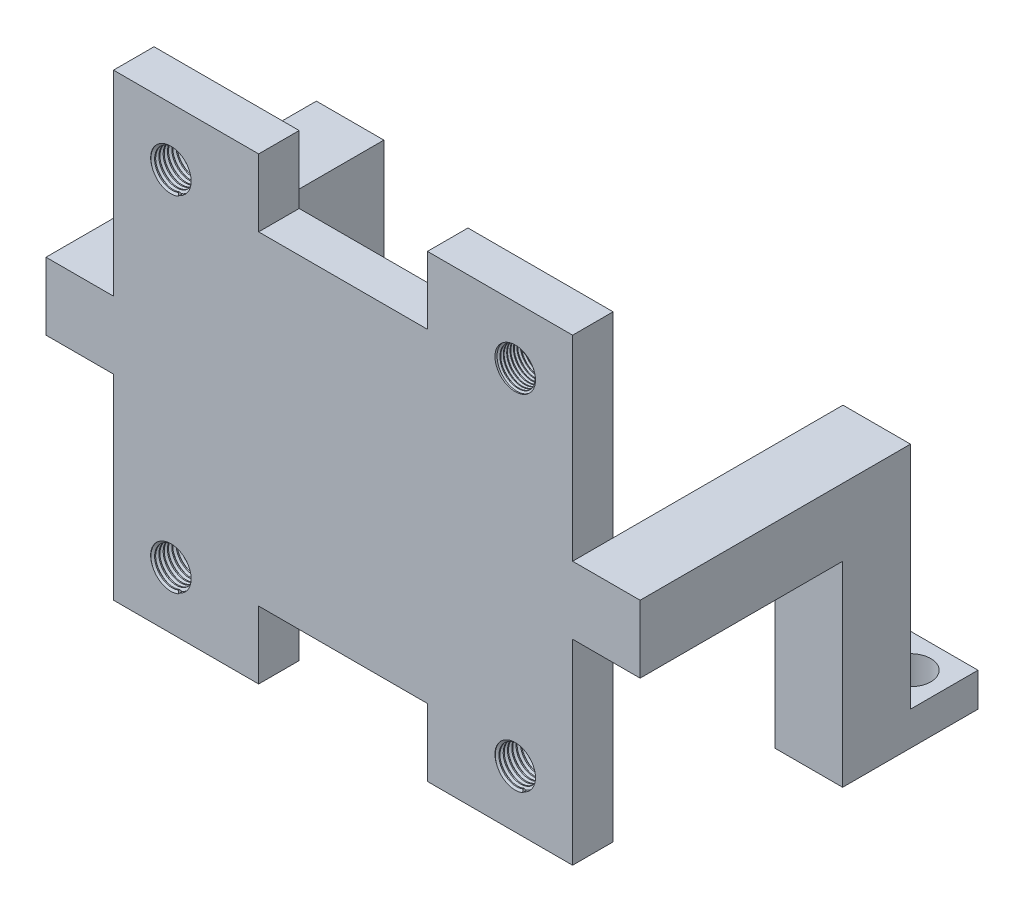
SolidWorks part; units mm, degrees
ref_plane "Front Plane" through (0, 0, 0) normal (0, 0, 1) x (1, 0, 0)
ref_plane "Top Plane" through (0, 0, 0) normal (0, 1, 0) x (1, 0, 0)
ref_plane "Right Plane" through (0, 0, 0) normal (1, 0, 0) x (0, 0, -1)
sketch "Sketch1" plane through (0, 0, 0) normal (0, 0, 1) x (1, 0, 0)
  line L0 (0, 0) -> (0, -34)
  line L1 (0, -34) -> (34, -34)
  line L2 (34, -34) -> (34, 0)
  line L3 (34, 0) -> (0, 0)
  dimension "D1" = 34
  dimension "D2" = 34
extrude "Boss-Extrude1" add sketch "Sketch1" along normal blind 3
sketch "Sketch2" plane through (0, 0, 0) normal (0, 0, -1) x (-1, 0, 0)
  line L0 (-17, 0) -> (-17, -34) construction
  line L1 (-34, 0) -> (0, 0) construction
  line L2 (0, -34) -> (-34, -34) construction
  line L3 (-34, -17) -> (0, -17) construction
  line L4 (-34, -34) -> (-34, 0) construction
  line L5 (0, 0) -> (0, -34) construction
  line L6 (-23.25, -5) -> (-10.75, -5)
  line L7 (-10.75, -5) -> (-10.75, 0)
  line L8 (-10.75, 0) -> (-23.25, 0)
  line L9 (-23.25, -5) -> (-23.25, 0)
  line L10 (-10.75, -29) -> (-10.75, -34)
  line L11 (-23.25, -29) -> (-10.75, -29)
  line L12 (-23.25, -29) -> (-23.25, -34)
  line L13 (-10.75, -34) -> (-23.25, -34)
  point P17 (-17, -5)
  dimension "D1" = 6.25
  dimension "D2" = 5
extrude "Cut-Extrude1" cut sketch "Sketch2" against normal through all contours L8 L9 L6 L7 | L10 L13 L12 L11
sketch "Sketch3" plane through (0, 0, 0) normal (0, 0, -1) x (-1, 0, 0)
  line L0 (-34, -34) -> (-34, 0) construction
  line L1 (-34, 0) -> (-23.25, 0) construction
  line L2 (-17, -5) -> (-17, -29) construction
  line L3 (-23.25, -5) -> (-10.75, -5) construction
  line L4 (-23.25, -29) -> (-10.75, -29) construction
  line L5 (-34, -17) -> (0, -17) construction
  line L6 (0, 0) -> (0, -34) construction
  circle A0 centre (-29.75, -4.25) radius 1.5
  circle A2 centre (-4.25, -4.25) radius 1.5
  circle A3 centre (-4.25, -29.75) radius 1.5
  circle A4 centre (-29.75, -29.75) radius 1.5
  dimension "D1" = 4.25
  dimension "D2" = 4.25
  dimension "D3" = 25.5
extrude "Cut-Extrude2" cut sketch "Sketch3" against normal through all contours A0 | A4 | A3 | A2
thread "Thread1" pitch 0.25 method extrude profile "Thread Profile1" start angle 0, offset 0, length 2.8, pitch 0.25, diameter 3
ref_plane "Plane1" through (31.25, -4.25, 0) normal (0, -1, 0) x (1, 0, 0)
sketch "Thread Profile1" plane through (31.25, -4.25, 0) normal (0, -1, 0) x (1, 0, 0)
  line L0 (0, 0) -> (0, 0.25) construction
  line L11 (0, 0) -> (0, 0.2187)
  line L12 (0, 0.2187) -> (-0.1353, 0.1406)
  line L13 (-0.1353, 0.1406) -> (-0.1353, 0.0781)
  line L15 (-0.1353, 0.0781) -> (0, 0)
  line L17 (-0.1353, 0.1094) -> (0, 0.1094) construction
  point P2 (0, 0)
  dimension "Pitch" = 0.25
  dimension "Profile_Angle" = 60
  dimension "Profile_Land" = 0.0625
  dimension "Profile_Height" = 0.1353
thread "Thread2" pitch 0.3175 method extrude profile "Thread Profile2" start angle 0, offset 0, length 2.8, pitch 0.3175, diameter 3
ref_plane "Plane2" through (5.75, -4.25, 0) normal (0, -1, 0) x (1, 0, 0)
sketch "Thread Profile2" plane through (5.75, -4.25, 0) normal (0, -1, 0) x (1, 0, 0)
  line L0 (0, 0) -> (0, 0.3175) construction
  line L11 (0, 0) -> (0, 0.2778)
  line L12 (0, 0.2778) -> (-0.1719, 0.1786)
  line L13 (-0.1719, 0.1786) -> (-0.1719, 0.0992)
  line L15 (-0.1719, 0.0992) -> (0, 0)
  line L17 (-0.1719, 0.1389) -> (0, 0.1389) construction
  point P2 (0, 0)
  dimension "Pitch" = 0.3175
  dimension "Profile_Angle" = 60
  dimension "Profile_Land" = 0.0794
  dimension "Profile_Height" = 0.1719
thread "Thread3" pitch 0.3175 method extrude profile "Thread Profile3" start angle 0, offset 0, length 2.8, pitch 0.3175, diameter 3
ref_plane "Plane3" through (5.75, -29.75, 0) normal (0, -1, 0) x (1, 0, 0)
sketch "Thread Profile3" plane through (5.75, -29.75, 0) normal (0, -1, 0) x (1, 0, 0)
  line L0 (0, 0) -> (0, 0.3175) construction
  line L11 (0, 0) -> (0, 0.2778)
  line L12 (0, 0.2778) -> (-0.1719, 0.1786)
  line L13 (-0.1719, 0.1786) -> (-0.1719, 0.0992)
  line L15 (-0.1719, 0.0992) -> (0, 0)
  line L17 (-0.1719, 0.1389) -> (0, 0.1389) construction
  point P2 (0, 0)
  dimension "Pitch" = 0.3175
  dimension "Profile_Angle" = 60
  dimension "Profile_Land" = 0.0794
  dimension "Profile_Height" = 0.1719
thread "Thread4" pitch 0.3175 method extrude profile "Thread Profile4" start angle 0, offset 0, length 2.8, pitch 0.3175, diameter 3
ref_plane "Plane4" through (31.25, -29.75, 0) normal (0, -1, 0) x (1, 0, 0)
sketch "Thread Profile4" plane through (31.25, -29.75, 0) normal (0, -1, 0) x (1, 0, 0)
  line L0 (0, 0) -> (0, 0.3175) construction
  line L11 (0, 0) -> (0, 0.2778)
  line L12 (0, 0.2778) -> (-0.1719, 0.1786)
  line L13 (-0.1719, 0.1786) -> (-0.1719, 0.0992)
  line L15 (-0.1719, 0.0992) -> (0, 0)
  line L17 (-0.1719, 0.1389) -> (0, 0.1389) construction
  point P2 (0, 0)
  dimension "Pitch" = 0.3175
  dimension "Profile_Angle" = 60
  dimension "Profile_Land" = 0.0794
  dimension "Profile_Height" = 0.1719
sketch "Sketch25" plane through (34, 0, 0) normal (1, 0, 0) x (0, 0, -1)
  line L0 (-3, -17) -> (0, -17) construction
  line L1 (-3, -34) -> (-3, 0) construction
  line L2 (0, -34) -> (0, 0) construction
  line L3 (-3, -17) -> (-3, -14.5)
  line L4 (-3, -14.5) -> (12, -14.5)
  line L11 (12, -14.5) -> (12, -19.5)
  line L12 (-3, -17) -> (-3, -19.5)
  line L13 (-3, -19.5) -> (12, -19.5)
  dimension "D1" = 2.5
  dimension "D2" = 15
  dimension "D4" = 5
extrude "Boss-Extrude2" add sketch "Sketch25" along normal blind 5
sketch "Sketch26" plane through (39, 0, 0) normal (1, 0, 0) x (0, 0, -1)
  line L0 (12, -14.5) -> (17.0235, -14.5)
  line L1 (17.0235, -14.5) -> (17.0235, -34)
  line L2 (17.0235, -34) -> (12, -34)
  line L3 (12, -34) -> (12, -14.5)
  dimension "D1" = 19.5
extrude "Boss-Extrude3" add sketch "Sketch26" against normal blind 5
sketch "Sketch28" plane through (39, 0, 0) normal (1, 0, 0) x (0, 0, -1)
  line L0 (17.0235, -34) -> (22.0235, -34)
  line L1 (22.0235, -34) -> (22.0235, -31.5)
  line L2 (22.0235, -31.5) -> (17.0235, -31.5)
  line L3 (17.0235, -34) -> (17.0235, -14.5) construction
  line L4 (17.0235, -31.5) -> (17.0235, -34)
  dimension "D1" = 5
  dimension "D2" = 2.5
extrude "Boss-Extrude4" add sketch "Sketch28" against normal blind 5
sketch "Sketch30" plane through (0, -31.5, 0) normal (0, 1, 0) x (1, 0, 0)
  line L0 (36.5, 22.0235) -> (36.5, 17.0235) construction
  line L1 (34, 22.0235) -> (39, 22.0235) construction
  line L2 (34, 17.0235) -> (39, 17.0235) construction
  circle A0 centre (36.5, 19.5235) radius 1.5
extrude "Cut-Extrude3" cut sketch "Sketch30" against normal through all
sketch "Sketch31" plane through (0, 0, 0) normal (0, 0, -1) x (-1, 0, 0)
  line L0 (-17, -5) -> (-17, -29) construction
  line L1 (-23.25, -5) -> (-10.75, -5) construction
  line L2 (-23.25, -29) -> (-10.75, -29) construction
sketch "Sketch32" plane through (0, 0, 0) normal (-1, 0, 0) x (0, 0, 1)
  line L0 (3, -14.5) -> (-17.0235, -14.5)
  line L1 (-17.0235, -14.5) -> (-17.0235, -31.5)
  line L2 (-17.0235, -31.5) -> (-22.0235, -31.5)
  line L3 (-22.0235, -31.5) -> (-22.0235, -34)
  line L4 (-22.0235, -34) -> (-12, -34)
  line L5 (-12, -34) -> (-12, -19.5)
  line L6 (-12, -19.5) -> (3, -19.5)
  line L7 (3, -19.5) -> (3, -14.5)
  dimension "D1" = 20.0235
  dimension "D2" = 17
  dimension "D3" = 5
  dimension "D4" = 15
  dimension "D5" = 10.0235
  dimension "D6" = 2.5
extrude "Boss-Extrude5" add sketch "Sketch32" along normal blind 5
sketch "Sketch33" plane through (0, -31.5, 0) normal (0, 1, 0) x (1, 0, 0)
  line L0 (-2.5, 22.0235) -> (-2.5, 17.0235) construction
  line L1 (-5, 22.0235) -> (0, 22.0235) construction
  line L2 (-5, 17.0235) -> (0, 17.0235) construction
  circle A0 centre (-2.5, 19.5235) radius 1.5
extrude "Cut-Extrude4" cut sketch "Sketch33" against normal through all
